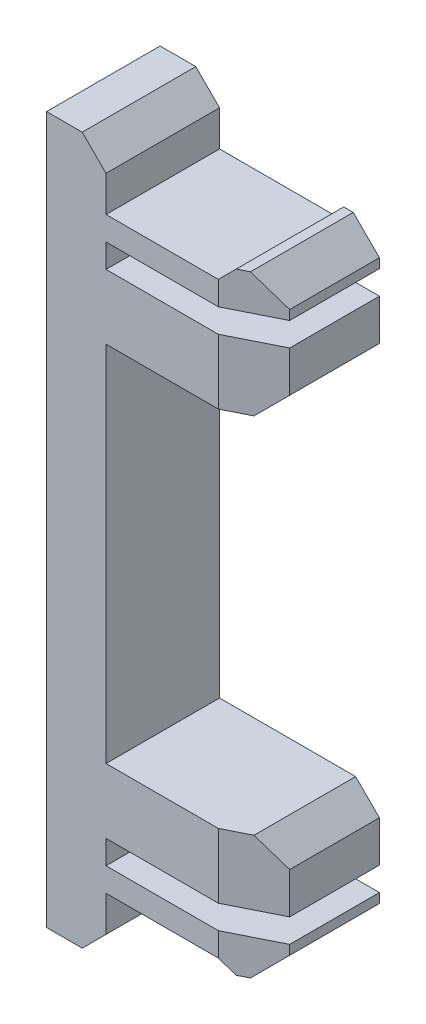
SolidWorks part; units mm, degrees
ref_plane "Front Plane" through (0, 0, 0) normal (0, 0, 1) x (1, 0, 0)
ref_plane "Top Plane" through (0, 0, 0) normal (0, 1, 0) x (1, 0, 0)
ref_plane "Right Plane" through (0, 0, 0) normal (1, 0, 0) x (0, 0, -1)
sketch "Sketch1" plane through (0, 0, 0) normal (0, 0, 1) x (1, 0, 0)
  line L0 (-2.6825, 9.7) -> (4.5875, 9.7)
  line L1 (-5.8575, -18.875) -> (5.8575, -18.875) construction
  line L2 (-5.8575, -18.875) -> (-5.8575, 18.875) construction
  line L3 (-5.8575, 18.875) -> (5.8575, 18.875) construction
  line L4 (5.8575, -18.875) -> (5.8575, 18.875) construction
  line L5 (-5.8575, -18.875) -> (5.8575, 18.875) construction
  line L6 (-5.8575, 18.875) -> (5.8575, -18.875) construction
  line L7 (-3.9525, -18.875) -> (-5.8575, -18.875)
  line L8 (-2.6825, -17.605) -> (-2.6825, 17.605)
  line L9 (-3.9525, 18.875) -> (-5.8575, 18.875)
  line L10 (-5.8575, -18.875) -> (-5.8575, 18.875)
  line L11 (-2.6825, -18.875) -> (-5.8575, 18.875) construction
  line L12 (-2.6825, 18.875) -> (-5.8575, -18.875) construction
  line L13 (5.8575, 9.7) -> (-2.6825, 9.7) construction
  line L14 (5.8575, 9.7) -> (5.8575, 15.7) construction
  line L15 (5.8575, 15.7) -> (-2.6825, 15.7) construction
  line L16 (-2.6825, 9.7) -> (-2.6825, 15.7) construction
  line L17 (5.8575, 9.7) -> (-2.6825, 15.7) construction
  line L18 (5.8575, 15.7) -> (-2.6825, 9.7) construction
  line L19 (5.8575, -15.7) -> (-2.6825, -15.7) construction
  line L20 (5.8575, -15.7) -> (5.8575, -9.7) construction
  line L21 (5.8575, -9.7) -> (-2.6825, -9.7) construction
  line L22 (-2.6825, -15.7) -> (-2.6825, -9.7) construction
  line L23 (5.8575, -15.7) -> (-2.6825, -9.7) construction
  line L24 (5.8575, -9.7) -> (-2.6825, -15.7) construction
  line L25 (5.8575, 10.97) -> (5.8575, 13.16)
  line L26 (5.8575, 13.16) -> (-2.6825, 13.16)
  line L27 (-2.6825, 15.7) -> (3.3175, 15.7)
  line L28 (3.3175, 15.7) -> (3.9525, 16.335)
  line L29 (3.9525, 16.335) -> (4.4605, 16.335)
  line L30 (4.4605, 16.335) -> (5.8575, 14.938)
  line L31 (5.8575, 14.938) -> (5.8575, 14.43)
  line L32 (5.8575, 14.43) -> (-2.6825, 14.43)
  line L33 (0, 0) -> (5.8575, 0) construction
  line L34 (4.5875, 9.7) -> (5.8575, 10.97)
  line L35 (4.5875, 9.7) -> (5.8575, 9.7) construction
  line L36 (5.8575, 9.7) -> (5.8575, 10.97) construction
  line L37 (-3.9525, 18.875) -> (-2.6825, 17.605)
  line L38 (-3.9525, -18.875) -> (-2.6825, -17.605)
  line L39 (-2.6825, 18.875) -> (-3.9525, 18.875) construction
  line L40 (-2.6825, 17.605) -> (-2.6825, 18.875) construction
  line L41 (-2.6825, -18.875) -> (-3.9525, -18.875) construction
  line L42 (-2.6825, -18.875) -> (-2.6825, -17.605) construction
  point P0 (0, 0)
  point P6 (-4.27, 0)
  point P7 (1.5875, -12.7)
  point P10 (1.5875, 12.7)
  point P29 (0.3175, 15.7)
  dimension "D1" = 3.175
  dimension "D2" = 6
  dimension "D3" = 6
  dimension "D4" = 25.4
  dimension "D5" = 45
  dimension "D6" = 45
  dimension "D7" = 0.508
  dimension "D8" = 6
  dimension "D9" = 0.635
  dimension "D10" = 1.27
  dimension "D11" = 0.762
  dimension "D12" = 1.27
  dimension "D13" = 3.175
  dimension "D14" = 1.27
  dimension "D15" = 1.27
  dimension "D16" = 45
  dimension "D17" = 1.27
extrude "Boss-Extrude1" add sketch "Sketch1" along normal mid plane 6.065 contours L8 L37 L9 L10 L7 L38
extrude "Boss-Extrude2" add sketch "Sketch1<3>" along normal up to surface and the other way up to surface contours L32 L31 L30 L29 L28 L27 L8 | L25 L26 L8 L0 region at (1.4796, 11.4667, 0) region at (1.6526, 15.1127, 0) up to face at (-4.1642, 0, 3.0325) other way up to face at (-4.1642, 0, -3.0325)
sketch "Sketch1<3>" plane through (0, 0, 0) normal (0, 0, 1) x (1, 0, 0) same geometry as "Sketch1"
sketch "Sketch2" plane through (0, 9.7, 0) normal (0, -1, 0) x (1, 0, 0)
  line L0 (3.3175, 3.0325) -> (5.8575, 1.7625)
  line L1 (4.5875, 3.0325) -> (-2.6825, 3.0325) construction
  line L2 (5.8575, 3.0325) -> (5.8575, -3.0325) construction
  line L3 (5.8575, 1.7625) -> (5.8575, 3.0325)
  line L4 (5.8575, 3.0325) -> (3.3175, 3.0325)
  dimension "D1" = 2.54
  dimension "D2" = 1.27
extrude "Cut-Extrude1" cut sketch "Sketch2" against normal through all
mirror "Mirror2" about plane through (0, 0, 0) normal (0, 1, 0) of bodies 104
equation "\"D1@Boss-Extrude1\"=.5in-6mm-.025in"
